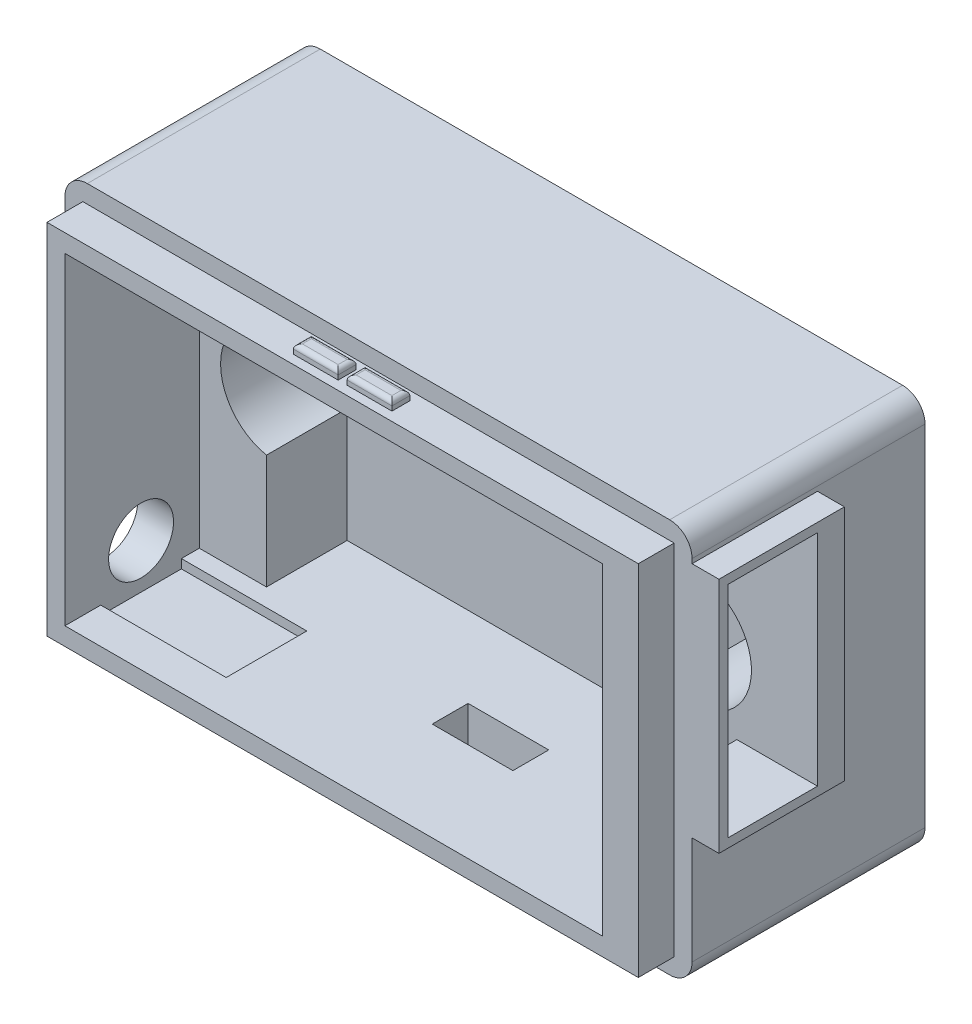
SolidWorks part; units mm, degrees
ref_plane "Front Plane" through (0, 0, 0) normal (0, 0, 1) x (1, 0, 0)
ref_plane "Top Plane" through (0, 0, 0) normal (0, 1, 0) x (1, 0, 0)
ref_plane "Right Plane" through (0, 0, 0) normal (1, 0, 0) x (0, 0, -1)
sketch "Sketch1" plane through (0, 0, 0) normal (0, 0, 1) x (1, 0, 0)
  line L1 (0, 0) -> (70, 0)
  line L2 (0, 0) -> (0, 44)
  line L3 (0, 44) -> (70, 44)
  line L4 (70, 0) -> (70, 44)
  dimension "D1" = 70
  dimension "D2" = 44
extrude "Mian Boss Extrude" add sketch "Sketch1" along normal blind 30
sketch "Sketch2" plane through (0, 0, 30) normal (0, 0, 1) x (1, 0, 0)
  line L0 (70, 44) -> (0, 44) construction
  line L1 (4, 40) -> (64, 40)
  line L2 (4, 40) -> (4, 4)
  line L3 (4, 4) -> (64, 4)
  line L4 (64, 40) -> (64, 4)
  line L5 (0, 0) -> (70, 0) construction
  line L6 (0, 44) -> (0, 0) construction
  line L7 (70, 0) -> (70, 44) construction
  dimension "D1" = 36
  dimension "D2" = 4
  dimension "D3" = 4
  dimension "D4" = 60
  dimension "D5" = 4
  dimension "D6" = 6
extrude "Main cut" cut sketch "Sketch2" against normal blind 15
sketch "Sketch4" plane through (0, 0, 15) normal (0, 0, 1) x (1, 0, 0)
  line L1 (11.5, 39) -> (56.5, 39)
  line L2 (11.5, 39) -> (11.5, 4)
  line L3 (11.5, 4) -> (56.5, 4)
  line L4 (56.5, 39) -> (56.5, 4)
  line L5 (4, 4) -> (64, 4) construction
  line L6 (4, 40) -> (4, 4) construction
  dimension "D1" = 35
  dimension "D2" = 45
  dimension "D3" = 0
  dimension "D4" = 7.5
extrude "Battery Cut" cut sketch "Sketch4" against normal blind 9
sketch "Sketch5" plane through (0, 0, 0) normal (0, 0, -1) x (-1, 0, 0)
  line L0 (-70, 0) -> (-70, 44) construction
  line L1 (0, 44) -> (0, 0) construction
  line L2 (-70, 44) -> (0, 44) construction
  line L3 (0, 0) -> (-70, 0) construction
  circle A0 centre (-59.25, 23) radius 6.375
  circle A1 centre (-12.75, 23) radius 6.375
  dimension "D1" = 12.75
  dimension "D2" = 12.75
  dimension "D4" = 10.75
  dimension "D5" = 21
  dimension "D6" = 21
  dimension "D7" = 12.75
  dimension "D8" = 23
  dimension "D9" = 23
  dimension "D3" = 46.5
extrude "Elctrode Cut" cut sketch "Sketch5" against normal blind 18
sketch "Sketch6" plane through (70, 0, 0) normal (1, 0, 0) x (0, 0, -1)
  line L0 (-30, 0) -> (-30, 44) construction
  line L1 (-25, 40) -> (-15, 40)
  line L2 (-25, 40) -> (-25, 15.5)
  line L3 (-25, 15.5) -> (-15, 15.5)
  line L4 (-15, 40) -> (-15, 15.5)
  line L5 (-30, 44) -> (0, 44) construction
  dimension "D1" = 5
  dimension "D2" = 4
  dimension "D3" = 24.5
  dimension "D4" = 10
extrude "USB-c Cut" cut sketch "Sketch6" against normal blind 7
sketch "Sketch7" plane through (0, 0, 0) normal (-1, 0, 0) x (0, 0, 1)
  line L0 (30, 44) -> (30, 0) construction
  line L1 (30, 44) -> (0, 44) construction
  circle A0 centre (21.5, 8) radius 3.625
  dimension "D1" = 7.25
  dimension "D3" = 36
  dimension "D2" = 8.5
extrude "Button Cut" cut sketch "Sketch7" against normal blind 7
sketch "Sketch8" plane through (0, 0, 0) normal (0, -1, 0) x (1, 0, 0)
  line L0 (70, 30) -> (70, 0) construction
  line L1 (34, 19) -> (43, 19)
  line L2 (34, 19) -> (34, 15)
  line L3 (34, 15) -> (43, 15)
  line L4 (43, 19) -> (43, 15)
  line L7 (0, 0) -> (70, 0) construction
  dimension "D1" = 9
  dimension "D2" = 4
  dimension "D3" = 27
  dimension "D4" = 15
extrude "Switch Cut" cut sketch "Sketch8" against normal blind 7
fillet "Outside Fillet" radius 2.5 4 edges at (70, 44, 15) (70, 0, 15) (0, 0, 15) (0, 44, 15)
sketch "Sketch10" plane through (0, 0, 30) normal (0, 0, 1) x (1, 0, 0)
  line L0 (67.5, 44) -> (2.5, 44) construction
  line L1 (2, 2) -> (68, 2)
  line L2 (2, 2) -> (2, 42)
  line L3 (2, 42) -> (68, 42)
  line L4 (68, 2) -> (68, 42)
  line L5 (0, 41.5) -> (0, 2.5) construction
  line L6 (70, 2.5) -> (70, 41.5) construction
  line L7 (2.5, 0) -> (67.5, 0) construction
  dimension "D1" = 2
  dimension "D2" = 2
  dimension "D3" = 2
  dimension "D4" = 2
extrude "Outer lid Extrude" cut sketch "Sketch10" against normal blind 4 flip side to cut
sketch "Sketch11" plane through (0, 2, 0) normal (0, -1, 0) x (1, 0, 0)
  line L0 (2, 30) -> (68, 30) construction
  line L1 (33.5, 27) -> (28.5, 27)
  line L2 (33.5, 27) -> (33.5, 29)
  line L3 (33.5, 29) -> (28.5, 29)
  line L4 (28.5, 27) -> (28.5, 29)
  line L5 (33.5, 27) -> (28.5, 29) construction
  line L6 (33.5, 29) -> (28.5, 27) construction
  line L7 (2, 26) -> (68, 26) construction
  line L8 (39.5, 27) -> (39.5, 29)
  line L13 (2, 26) -> (2, 30) construction
  line L14 (39.5, 27) -> (34.5, 27)
  line L15 (34.5, 27) -> (34.5, 29)
  line L16 (39.5, 29) -> (34.5, 29)
  line L17 (33.5, 27) -> (39.5, 27) construction
  line L18 (68, 26) -> (68, 30) construction
  point P0 (31, 28)
  dimension "D1" = 1
  dimension "D2" = 1
  dimension "D3" = 26.5
  dimension "D4" = 5
  dimension "D5" = 2
  dimension "D7" = 28.5
  dimension "D8" = 2
  dimension "D6" = 5
  dimension "D9" = 6
extrude "Lid Snap-Extrude" add sketch "Sketch11" along normal blind 1 and the other way blind 41
sketch "Sketch13" plane through (0, 0, 29) normal (0, 0, 1) x (1, 0, 0)
  line L1 (28.5, 40) -> (39.5, 40)
  line L2 (28.5, 40) -> (28.5, 4)
  line L3 (28.5, 4) -> (39.5, 4)
  line L4 (39.5, 40) -> (39.5, 4)
extrude "Inner Lid-Extrude" cut sketch "Sketch13" against normal blind 3
sketch "Sketch14" plane through (70, 0, 0) normal (1, 0, 0) x (0, 0, -1)
  line L1 (-26, 41) -> (-12, 41)
  line L2 (-26, 41) -> (-26, 14.5)
  line L3 (-26, 14.5) -> (-12, 14.5)
  line L4 (-12, 41) -> (-12, 14.5)
  line L5 (-26, 2.5) -> (-26, 41.5) construction
  line L7 (-25, 40) -> (-25, 15.5) construction
  line L9 (-25, 40) -> (-15, 40)
  line L10 (-25, 40) -> (-25, 15.5)
  line L11 (-25, 15.5) -> (-15, 15.5)
  line L12 (-15, 40) -> (-15, 15.5)
  dimension "D1" = 14
  dimension "D2" = 0
extrude "USB Cover-Extrude" add sketch "Sketch14" along normal blind 3
sketch "Sketch15" plane through (0, 4, 0) normal (0, 1, 0) x (1, 0, 0)
  line L0 (4, -15) -> (4, -30) construction
  line L1 (4, -17) -> (8, -17)
  line L2 (4, -17) -> (4, -26)
  line L3 (4, -26) -> (8, -26)
  line L4 (8, -17) -> (8, -26)
  line L5 (4, -30) -> (64, -30) construction
  dimension "D1" = 0
  dimension "D2" = 4
  dimension "D3" = 9
  dimension "D4" = 4
extrude "Button side cut" cut sketch "Sketch15" against normal blind 1
chamfer "Chamfer1" distance 10 angle 45 1 edges at (8, 4, 21.5)
fillet "Lid Snap Fillet" radius 0.5 16 edges at (34.5, 43, 28) (37, 43, 27) (39.5, 43, 28) (37, 43, 29) (31, 43, 27) (33.5, 43, 28) (31, 43, 29) (28.5, 43, 28) (31, 1, 29) (33.5, 1, 28) (31, 1, 27) (28.5, 1, 28) (39.5, 1, 28) (37, 1, 27) (34.5, 1, 28) (37, 1, 29)
